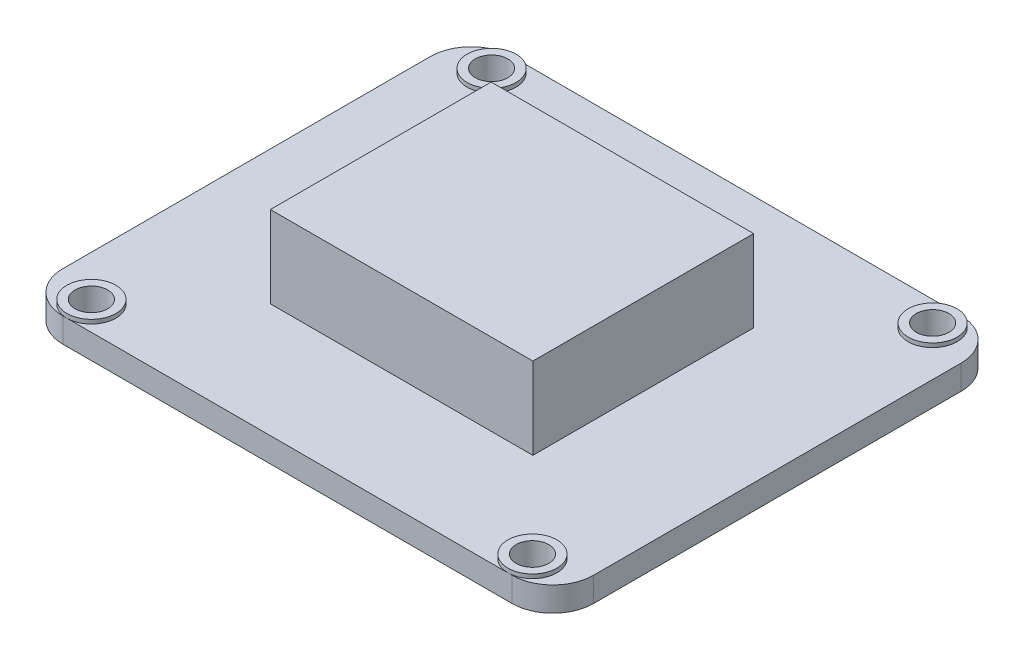
SolidWorks part; units mm, degrees
ref_plane "前视基准面" through (0, 0, 0) normal (0, 0, 1) x (1, 0, 0)
ref_plane "上视基准面" through (0, 0, 0) normal (0, 1, 0) x (1, 0, 0)
ref_plane "右视基准面" through (0, 0, 0) normal (1, 0, 0) x (0, 0, -1)
sketch "草图2" plane through (0, 0, 0) normal (0, 1, 0) x (1, 0, 0)
  line L0 (-28.8543, 28.5882) -> (-28.8543, -26.4118)
  line L1 (-34.3543, 28.5882) -> (30.6457, 28.5882)
  line L2 (-34.3543, 28.5882) -> (-34.3543, -26.4118)
  line L3 (-34.3543, -26.4118) -> (30.6457, -26.4118)
  line L4 (30.6457, 28.5882) -> (30.6457, -26.4118)
  line L5 (-34.3543, 25.5882) -> (30.6457, 25.5882)
  line L6 (-34.3543, -23.4118) -> (30.6457, -23.4118)
  line L7 (25.1457, 28.5882) -> (25.1457, -26.4118)
  line L8 (-1.8543, 25.5882) -> (-1.8543, -23.4118)
  line L10 (-17.9233, -12.4285) -> (14.2147, -12.4285)
  line L11 (-17.9233, -12.4285) -> (-17.9233, 14.605)
  line L12 (-17.9233, 14.605) -> (14.2147, 14.605)
  line L13 (14.2147, -12.4285) -> (14.2147, 14.605)
  line L14 (-17.9233, -12.4285) -> (14.2147, 14.605) construction
  line L15 (-17.9233, 14.605) -> (14.2147, -12.4285) construction
  circle A0 centre (-28.8543, 25.5882) radius 2
  circle A1 centre (-28.8543, 25.5882) radius 3
  circle A2 centre (25.1457, 25.5882) radius 2
  circle A3 centre (25.1457, 25.5882) radius 3
  circle A4 centre (25.1457, -23.4118) radius 2
  circle A5 centre (25.1457, -23.4118) radius 3
  circle A6 centre (-28.8543, -23.4118) radius 2
  circle A7 centre (-28.8543, -23.4118) radius 3
  point P26 (-1.8543, 1.0882)
  dimension "D1" = 65
  dimension "D2" = 55
  dimension "D3" = 3
  dimension "D4" = 3
  dimension "D5" = 5.5
  dimension "D6" = 5.5
extrude "凸台-拉伸1" add sketch "草图2" along normal blind 10 contours L10 L13 L12 L8 | L12 L11 L10 L8 region at (6.1802, 0, -1.0882) region at (-9.8888, 0, -1.0882)
extrude "凸台-拉伸2" add sketch "草图2<3>" against normal blind 3 contours L2 L3 L4 L1
sketch "草图2<3>" plane through (0, 0, 0) normal (0, 1, 0) x (1, 0, 0) same geometry as "草图2"
extrude "切除-拉伸1" cut sketch "草图2<5>" against normal blind 3 contours A4
sketch "草图2<5>" plane through (0, 0, 0) normal (0, 1, 0) x (1, 0, 0) same geometry as "草图2"
extrude "切除-拉伸2" cut sketch "草图2<6>" against normal blind 3 contours A6
sketch "草图2<6>" plane through (0, 0, 0) normal (0, 1, 0) x (1, 0, 0) same geometry as "草图2"
extrude "切除-拉伸3" cut sketch "草图2<7>" against normal blind 3 contours A2
sketch "草图2<7>" plane through (0, 0, 0) normal (0, 1, 0) x (1, 0, 0) same geometry as "草图2"
extrude "切除-拉伸4" cut sketch "草图2<8>" against normal blind 3 contours A0
sketch "草图2<8>" plane through (0, 0, 0) normal (0, 1, 0) x (1, 0, 0) same geometry as "草图2"
extrude "凸台-拉伸3" add sketch "草图2<12>" along normal blind 0.5 contours L7 A3 L5 A2 | L5 A3 L7 A2 | L7 A3 L5 A2 | L5 A3 L7 A2 region at (26.7585, 0, -27.201) region at (23.5329, 0, -27.201) region at (26.7585, 0, -23.9755) region at (23.5329, 0, -23.9755)
sketch "草图2<12>" plane through (0, 0, 0) normal (0, 1, 0) x (1, 0, 0) same geometry as "草图2"
extrude "凸台-拉伸5" add sketch "草图2<15>" along normal blind 0.5 contours L6 A5 L7 A4 | L7 A5 L6 A4 | L6 A5 L7 A4 | L7 A5 L6 A4 region at (26.7585, 0, 21.799) region at (23.5329, 0, 21.799) region at (26.7585, 0, 25.0245) region at (23.5329, 0, 25.0245)
sketch "草图2<15>" plane through (0, 0, 0) normal (0, 1, 0) x (1, 0, 0) same geometry as "草图2"
extrude "凸台-拉伸6" add sketch "草图2<16>" along normal blind 0.5 contours L6 A7 L0 A6 | L0 A7 L6 A6 | L6 A7 L0 A6 | L0 A7 L6 A6 region at (-27.2415, 0, 21.799) region at (-30.4671, 0, 21.799) region at (-30.4671, 0, 25.0245) region at (-27.2415, 0, 25.0245)
sketch "草图2<16>" plane through (0, 0, 0) normal (0, 1, 0) x (1, 0, 0) same geometry as "草图2"
extrude "凸台-拉伸7" add sketch "草图2<17>" along normal blind 0.5 contours L0 A1 L5 A0 | L5 A1 L0 A0 | L5 A1 L0 A0 | L0 A1 L5 A0 region at (-27.2415, 0, -27.201) region at (-30.4671, 0, -27.201) region at (-27.2415, 0, -23.9755) region at (-30.4671, 0, -23.9755)
sketch "草图2<17>" plane through (0, 0, 0) normal (0, 1, 0) x (1, 0, 0) same geometry as "草图2"
fillet "圆角3" radius 5 1 edges at (30.6457, -1.5, -28.5882) type face fillet first side face at (30.6457, -1.5, -1.0882) second side face at (-1.8543, -1, -28.5882)
fillet "圆角4" radius 5 1 edges at (30.6457, -1.5, 26.4118)
fillet "圆角5" radius 5 1 edges at (-34.3543, -1.5, 26.4118)
fillet "圆角6" radius 5 1 edges at (-34.3543, -1.5, -28.5882)
sketch "草图4" plane through (0, -3, 0) normal (0, -1, 0) x (1, 0, 0)
  line L0 (-1.8543, -28.5882) -> (-1.8543, 26.4118)
  line L3 (-34.3543, -1.0882) -> (30.6457, -1.0882)
  line L4 (-34.3543, -23.5882) -> (-34.3543, 21.4118) construction
  line L5 (30.6457, -23.5882) -> (30.6457, 21.4118) construction
  line L6 (-29.3543, -28.5882) -> (25.6457, -28.5882) construction
  line L7 (-29.3543, 26.4118) -> (25.6457, 26.4118) construction
